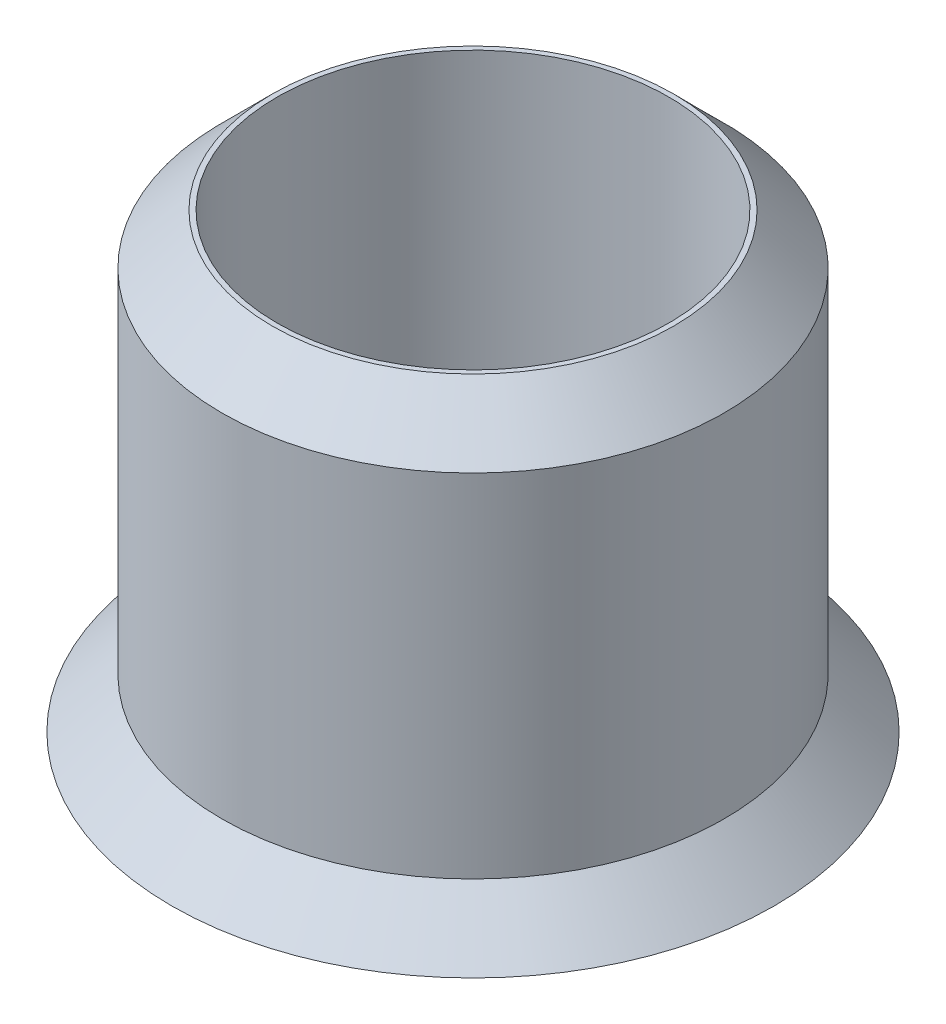
SolidWorks part; units mm, degrees
ref_plane "Спереди" through (0, 0, 0) normal (0, 0, 1) x (1, 0, 0)
ref_plane "Сверху" through (0, 0, 0) normal (0, 1, 0) x (1, 0, 0)
ref_plane "Справа" through (0, 0, 0) normal (1, 0, 0) x (0, 0, -1)
sketch "Эскиз1" plane through (0, 0, 0) normal (0, 1, 0) x (1, 0, 0)
  circle A0 centre (0, 0) radius 6
  dimension "D1" = 12
extrude "Бобышка-Вытянуть1" add sketch "Эскиз1" along normal blind 1
sketch "Эскиз2" plane through (0, 1, 0) normal (0, 1, 0) x (1, 0, 0)
  circle A0 centre (0, 0) radius 5
  circle A1 centre (0, 0) radius 3.9
  dimension "D1" = 10
  dimension "D2" = 7.8
extrude "Бобышка-Вытянуть2" add sketch "Эскиз2" along normal blind 8
chamfer "Фаска1" distance 1 angle 45 1 edges at (0, 1, 6)
chamfer "Фаска2" distance 1 angle 45 1 edges at (0, 9, 5)
